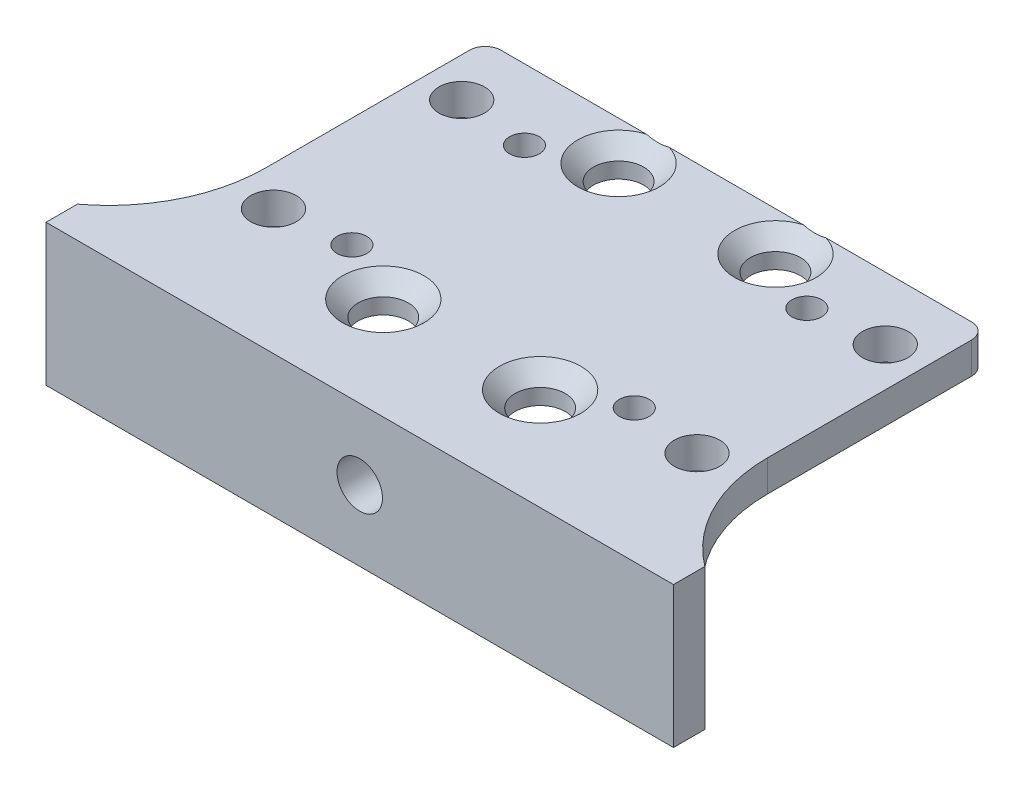
SolidWorks part; units mm, degrees
ref_plane "Front Plane" through (0, 0, 0) normal (0, 0, 1) x (1, 0, 0)
ref_plane "Top Plane" through (0, 0, 0) normal (0, 1, 0) x (1, 0, 0)
ref_plane "Right Plane" through (0, 0, 0) normal (1, 0, 0) x (0, 0, -1)
sketch "Sketch1" plane through (0, 0, 0) normal (0, 1, 0) x (1, 0, 0)
  line L1 (-16, -10) -> (16, -10)
  line L2 (-16, -10) -> (-16, 10)
  line L3 (-16, 10) -> (16, 10)
  line L4 (16, -10) -> (16, 10)
  line L5 (-16, -10) -> (16, 10) construction
  line L6 (-16, 10) -> (16, -10) construction
  circle A0 centre (-5, 7.5) radius 1.6
  circle A1 centre (5, 7.5) radius 1.6
  circle A2 centre (-5, -7.5) radius 1.6
  circle A3 centre (5, -7.5) radius 1.6
  point P12 (0, 0)
  dimension "D3" = 3.2
  dimension "D1" = 10
  dimension "D2" = 15
  dimension "D4" = 5
  dimension "D5" = 7.5
  dimension "D6" = 32
  dimension "D7" = 20
extrude "Boss-Extrude1" add sketch "Sketch1" along normal blind 2
sketch "Sketch3" plane through (0, 0, 10) normal (0, 0, 1) x (1, 0, 0)
  line L0 (-16, 2) -> (16, 2) construction
  line L1 (-20, 2) -> (20, 2)
  line L2 (-20, 2) -> (-20, -7)
  line L3 (-20, -7) -> (20, -7)
  line L4 (20, 2) -> (20, -7)
  circle A0 centre (0, -2.5) radius 1.45
  point P6 (0, 2)
  dimension "D3" = 2.9
  dimension "D1" = 40
  dimension "D2" = 9
  dimension "D4" = 4.5
extrude "Boss-Extrude2" add sketch "Sketch3" along normal blind 4
sketch "Sketch4" plane through (0, 0, 10) normal (0, 0, -1) x (-1, 0, 0)
  line L0 (-16, 2) -> (-20, 2)
  line L1 (-20, 2) -> (-20, -7)
  line L2 (-20, -7) -> (20, -7)
  line L3 (20, -7) -> (20, 2)
  line L4 (20, 2) -> (16, 2)
  line L5 (16, 2) -> (16, 0)
  line L6 (-16, 2) -> (-16, 0)
  line L7 (-16, 0) -> (-4, 0)
  line L8 (-16, 0) -> (16, 0) construction
  line L9 (-4, 0) -> (-4, -2.5)
  line L10 (16, 0) -> (4, 0)
  line L11 (4, 0) -> (4, -2.5)
  arc A0 (-4, -2.5) -> (4, -2.5) centre (0, -2.5) ccw
  circle A1 centre (0, -2.5) radius 1.45 construction
  dimension "D1" = 8
extrude "Cut-Extrude1" cut sketch "Sketch4" against normal blind 2
fillet "Fillet1" radius 10 2 edges at (16, 1, 12) (-16, 1, 12)
chamfer "Chamfer1" distance 1 angle 45 4 edges at (-5, 2, 9.1) (5, 2, 9.1) (5, 2, -5.9) (-5, 2, -5.9)
sketch "Sketch12" plane through (0, 2, 0) normal (0, 1, 0) x (1, 0, 0)
  line L1 (-11, 20.5) -> (11, 20.5) construction
  line L2 (-11, 20.5) -> (-11, -7.5) construction
  line L3 (-11, -7.5) -> (11, -7.5) construction
  line L4 (11, 20.5) -> (11, -7.5) construction
  circle A0 centre (0, 0) radius 8 construction
  circle A1 centre (-13.5, 6) radius 1.45
  circle A2 centre (-13.5, -6) radius 1.45
  circle A3 centre (13.5, -6) radius 1.45
  circle A4 centre (13.5, 6) radius 1.45
  circle A5 centre (-9, 5.5) radius 0.95
  circle A6 centre (9, 5.5) radius 0.95
  circle A7 centre (9, -5.5) radius 0.95
  circle A8 centre (-9, -5.5) radius 0.95
  point P19 (0, -7.5)
  dimension "D1" = 16
  dimension "D2" = 2.9
  dimension "D11" = 1.9
  dimension "D4" = 12
  dimension "D5" = 13.5
  dimension "D3" = 27
  dimension "D6" = 6
  dimension "D7" = 18
  dimension "D8" = 11
  dimension "D9" = 9
  dimension "D10" = 5.5
  dimension "D12" = 22
  dimension "D13" = 28
  dimension "D14" = 2
extrude "Cut-Extrude2" cut sketch "Sketch12" against normal up to next
fillet "Fillet2" radius 1 2 edges at (16, 1, -10) (-16, 1, -10)
thread "Thread1" pitch 0.7 start angle 0, offset 0, length 0, pitch 0.7, diameter 3.3
ref_plane "Plane1" through (1.65, -2.5, 10) normal (0, -1, 0) x (1, 0, 0)
sketch "Thread Profile1" plane through (1.65, -2.5, 10) normal (0, -1, 0) x (1, 0, 0)
  line L0 (0, 0) -> (0, 0.7) construction
  line L1 (0, 0) -> (0.3789, 0.2187)
  line L2 (0.3789, 0.2187) -> (0.3789, 0.3062)
  line L3 (0.3789, 0.3062) -> (0, 0.525)
  line L4 (0.3789, 0.2625) -> (0, 0.2625) construction
  line L11 (0, 0) -> (0, 0.525)
  point P2 (0, 0)
  dimension "Pitch" = 0.7
  dimension "Profile_Angle" = 60
  dimension "Profile_Land" = 0.0875
  dimension "Profile_Height" = 0.3789
thread "Thread2" pitch 0.5 start angle 0, offset 0, length 0, pitch 0.5, diameter 2.5
ref_plane "Plane3" through (14.75, 0, -6) normal (0, 0, 1) x (1, 0, 0)
sketch "Thread Profile3" plane through (14.75, 0, -6) normal (0, 0, 1) x (1, 0, 0)
  line L0 (0, 0) -> (0, 0.5) construction
  line L1 (0, 0) -> (0.2706, 0.1562)
  line L2 (0.2706, 0.1562) -> (0.2706, 0.2187)
  line L3 (0.2706, 0.2187) -> (0, 0.375)
  line L4 (0.2706, 0.1875) -> (0, 0.1875) construction
  line L11 (0, 0) -> (0, 0.375)
  point P2 (0, 0)
  dimension "Pitch" = 0.5
  dimension "Profile_Angle" = 60
  dimension "Profile_Land" = 0.0625
  dimension "Profile_Height" = 0.2706
thread "Thread3" pitch 0.5 start angle 0, offset 0, length 0, pitch 0.5, diameter 2.5
ref_plane "Plane5" through (-12.25, 0, -6) normal (0, 0, 1) x (1, 0, 0)
sketch "Thread Profile5" plane through (-12.25, 0, -6) normal (0, 0, 1) x (1, 0, 0)
  line L0 (0, 0) -> (0, 0.5) construction
  line L1 (0, 0) -> (0.2706, 0.1562)
  line L2 (0.2706, 0.1562) -> (0.2706, 0.2187)
  line L3 (0.2706, 0.2187) -> (0, 0.375)
  line L4 (0.2706, 0.1875) -> (0, 0.1875) construction
  line L11 (0, 0) -> (0, 0.375)
  point P2 (0, 0)
  dimension "Pitch" = 0.5
  dimension "Profile_Angle" = 60
  dimension "Profile_Land" = 0.0625
  dimension "Profile_Height" = 0.2706
thread "Thread4" pitch 0.5 start angle 0, offset 0, length 0, pitch 0.5, diameter 2.5
ref_plane "Plane6" through (-12.25, 0, 6) normal (0, 0, 1) x (1, 0, 0)
sketch "Thread Profile6" plane through (-12.25, 0, 6) normal (0, 0, 1) x (1, 0, 0)
  line L0 (0, 0) -> (0, 0.5) construction
  line L1 (0, 0) -> (0.2706, 0.1562)
  line L2 (0.2706, 0.1562) -> (0.2706, 0.2187)
  line L3 (0.2706, 0.2187) -> (0, 0.375)
  line L4 (0.2706, 0.1875) -> (0, 0.1875) construction
  line L11 (0, 0) -> (0, 0.375)
  point P2 (0, 0)
  dimension "Pitch" = 0.5
  dimension "Profile_Angle" = 60
  dimension "Profile_Land" = 0.0625
  dimension "Profile_Height" = 0.2706
thread "Thread5" pitch 0.5 start angle 0, offset 0, length 0, pitch 0.5, diameter 2.5
ref_plane "Plane7" through (14.75, 0, 6) normal (0, 0, 1) x (1, 0, 0)
sketch "Thread Profile7" plane through (14.75, 0, 6) normal (0, 0, 1) x (1, 0, 0)
  line L0 (0, 0) -> (0, 0.5) construction
  line L1 (0, 0) -> (0.2706, 0.1562)
  line L2 (0.2706, 0.1562) -> (0.2706, 0.2187)
  line L3 (0.2706, 0.2187) -> (0, 0.375)
  line L4 (0.2706, 0.1875) -> (0, 0.1875) construction
  line L11 (0, 0) -> (0, 0.375)
  point P2 (0, 0)
  dimension "Pitch" = 0.5
  dimension "Profile_Angle" = 60
  dimension "Profile_Land" = 0.0625
  dimension "Profile_Height" = 0.2706
thread "Thread6" pitch 0.45 start angle 0, offset 0, length 0, pitch 0.45, diameter 2.05
ref_plane "Plane8" through (-7.975, 0, -5.5) normal (0, 0, 1) x (1, 0, 0)
sketch "Thread Profile8" plane through (-7.975, 0, -5.5) normal (0, 0, 1) x (1, 0, 0)
  line L0 (0, 0) -> (0, 0.45) construction
  line L1 (0, 0) -> (0.2436, 0.1406)
  line L2 (0.2436, 0.1406) -> (0.2436, 0.1969)
  line L3 (0.2436, 0.1969) -> (0, 0.3375)
  line L4 (0.2436, 0.1687) -> (0, 0.1687) construction
  line L11 (0, 0) -> (0, 0.3375)
  point P2 (0, 0)
  dimension "Pitch" = 0.45
  dimension "Profile_Angle" = 60
  dimension "Profile_Land" = 0.0562
  dimension "Profile_Height" = 0.2436
thread "Thread7" pitch 0.45 start angle 0, offset 0, length 0, pitch 0.45, diameter 2.05
ref_plane "Plane9" through (10.025, 0, -5.5) normal (0, 0, 1) x (1, 0, 0)
sketch "Thread Profile9" plane through (10.025, 0, -5.5) normal (0, 0, 1) x (1, 0, 0)
  line L0 (0, 0) -> (0, 0.45) construction
  line L1 (0, 0) -> (0.2436, 0.1406)
  line L2 (0.2436, 0.1406) -> (0.2436, 0.1969)
  line L3 (0.2436, 0.1969) -> (0, 0.3375)
  line L4 (0.2436, 0.1687) -> (0, 0.1687) construction
  line L11 (0, 0) -> (0, 0.3375)
  point P2 (0, 0)
  dimension "Pitch" = 0.45
  dimension "Profile_Angle" = 60
  dimension "Profile_Land" = 0.0562
  dimension "Profile_Height" = 0.2436
thread "Thread8" pitch 0.45 start angle 0, offset 0, length 0, pitch 0.45, diameter 2.05
ref_plane "Plane10" through (-7.975, 0, 5.5) normal (0, 0, 1) x (1, 0, 0)
sketch "Thread Profile10" plane through (-7.975, 0, 5.5) normal (0, 0, 1) x (1, 0, 0)
  line L0 (0, 0) -> (0, 0.45) construction
  line L1 (0, 0) -> (0.2436, 0.1406)
  line L2 (0.2436, 0.1406) -> (0.2436, 0.1969)
  line L3 (0.2436, 0.1969) -> (0, 0.3375)
  line L4 (0.2436, 0.1687) -> (0, 0.1687) construction
  line L11 (0, 0) -> (0, 0.3375)
  point P2 (0, 0)
  dimension "Pitch" = 0.45
  dimension "Profile_Angle" = 60
  dimension "Profile_Land" = 0.0562
  dimension "Profile_Height" = 0.2436
thread "Thread9" pitch 0.45 start angle 0, offset 0, length 0, pitch 0.45, diameter 2.05
ref_plane "Plane11" through (10.025, 0, 5.5) normal (0, 0, 1) x (1, 0, 0)
sketch "Thread Profile11" plane through (10.025, 0, 5.5) normal (0, 0, 1) x (1, 0, 0)
  line L0 (0, 0) -> (0, 0.45) construction
  line L1 (0, 0) -> (0.2436, 0.1406)
  line L2 (0.2436, 0.1406) -> (0.2436, 0.1969)
  line L3 (0.2436, 0.1969) -> (0, 0.3375)
  line L4 (0.2436, 0.1687) -> (0, 0.1687) construction
  line L11 (0, 0) -> (0, 0.3375)
  point P2 (0, 0)
  dimension "Pitch" = 0.45
  dimension "Profile_Angle" = 60
  dimension "Profile_Land" = 0.0562
  dimension "Profile_Height" = 0.2436
equation "\"D4@Sketch1\"=\"D1@Sketch1\"/2"
equation "\"D5@Sketch1\"=\"D2@Sketch1\"/2"
equation "\"D4@Sketch3\"=\"D2@Sketch3\"/2"
equation "\"D5@Sketch12\"=\"D3@Sketch12\"/2"
equation "\"D6@Sketch12\"=\"D4@Sketch12\"/2"
equation "\"D9@Sketch12\"=\"D7@Sketch12\"/2"
equation "\"D10@Sketch12\"=\"D8@Sketch12\"/2"
